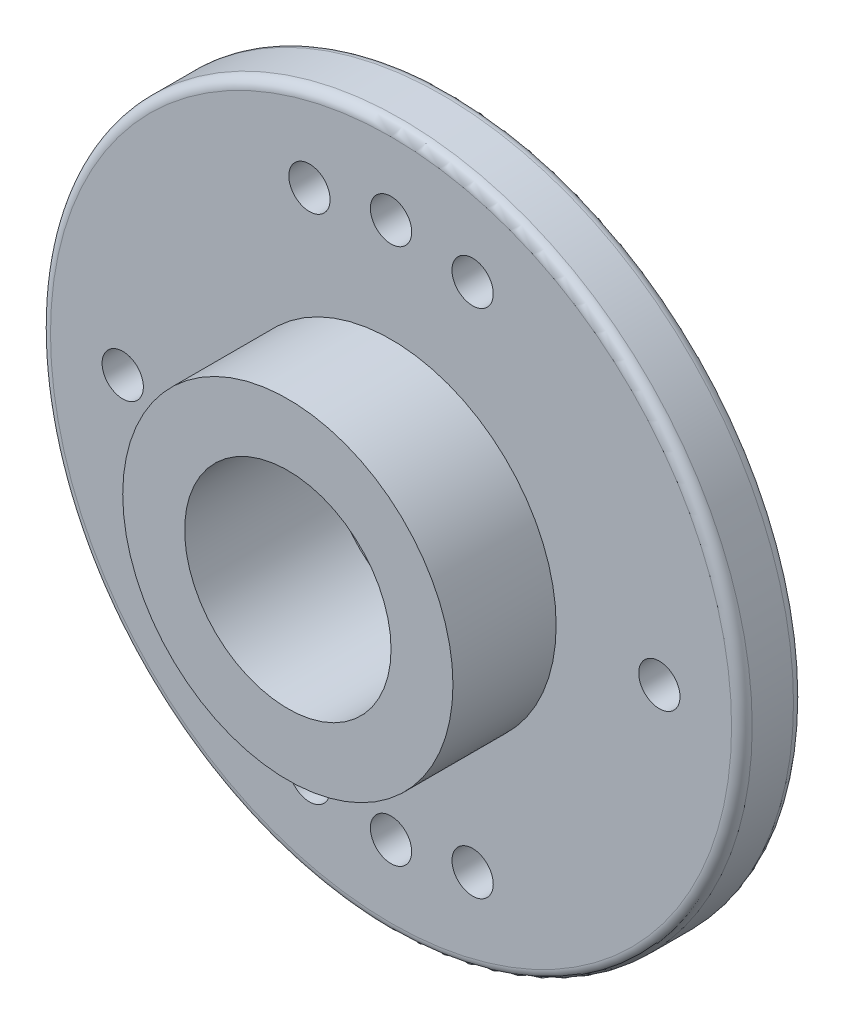
SolidWorks part; units mm, degrees
material "Nylon 101"
ref_plane "Front Plane" through (0, 0, 0) normal (0, 0, 1) x (1, 0, 0)
ref_plane "Top Plane" through (0, 0, 0) normal (0, 1, 0) x (1, 0, 0)
ref_plane "Right Plane" through (0, 0, 0) normal (1, 0, 0) x (0, 0, -1)
sketch "Sketch1" plane through (0, 0, 0) normal (0, 0, 1) x (1, 0, 0)
  line L0 (-8.5, 0) -> (8.5, 0) construction
  line L1 (0, 8.5) -> (0, -8.5) construction
  line L2 (-2.5842, 8.0976) -> (0, 0) construction
  line L3 (2.5842, 8.0976) -> (0, 0) construction
  line L4 (0, 0) -> (-2.5842, -8.0976) construction
  line L5 (0, 0) -> (2.5842, -8.0976) construction
  circle A0 centre (0, 0) radius 8.5
  circle A1 centre (0, 0) radius 1.25
  circle A2 centre (0, 0) radius 3
  circle A3 centre (0, 0) radius 3.5
  circle A4 centre (0, 6.5) radius 0.5
  circle A5 centre (0, -6.5) radius 0.5
  circle A6 centre (-6.5, 0) radius 0.5
  circle A7 centre (6.5, 0) radius 0.5
  circle A8 centre (-1.9762, 6.1923) radius 0.5
  circle A9 centre (1.9762, 6.1923) radius 0.5
  circle A10 centre (-1.9762, -6.1923) radius 0.5
  circle A11 centre (1.9762, -6.1923) radius 0.5
  circle A12 centre (0, 0) radius 4
  circle A13 centre (0, 0) radius 2.5
  dimension "D1" = 17
  dimension "D2" = 2.5
  dimension "D3" = 6
  dimension "D4" = 7
  dimension "D5" = 1
  dimension "D16" = 8
  dimension "D17" = 5
  dimension "D6" = 2
  dimension "D7" = 2
  dimension "D8" = 2
  dimension "D9" = 2
  dimension "D10" = 2
  dimension "D11" = 2
  dimension "D12" = 2
  dimension "D13" = 2
  dimension "D14" = 2
  dimension "D15" = 2
extrude "Boss-Extrude1" add sketch "Sketch1" along normal blind 0.5 contours A0 A12 A11 A10 A9 A8 A7 A6 A5 A4 | A12 A3 | A3 A2 | A2 A13 | A13 A1 region at (-8.2596, 0, 0) region at (-2.9151, 0, 0) region at (-3.401, 0, 0) region at (-3.8869, 0, 0) region at (-2.4293, 0, 0)
extrude "Boss-Extrude2" add sketch "Sketch1<4>" along normal blind 1.5 contours A0 A12 A11 A10 A9 A8 A7 A6 A5 A4 | A12 A3 | A3 A2 | A2 A13 region at (-8.2596, 0, 0) region at (-2.9151, 0, 0) region at (-3.401, 0, 0) region at (-3.8869, 0, 0)
sketch "Sketch1<4>" plane through (0, 0, 0) normal (0, 0, 1) x (1, 0, 0) same geometry as "Sketch1"
extrude "Boss-Extrude3" add sketch "Sketch1<5>" along normal blind 4 contours A12 A3 | A3 A2 | A2 A13 region at (-2.9151, 0, 0) region at (-3.401, 0, 0) region at (-3.8869, 0, 0)
sketch "Sketch1<5>" plane through (0, 0, 0) normal (0, 0, 1) x (1, 0, 0) same geometry as "Sketch1"
extrude "Boss-Extrude4" add sketch "Sketch1<6>" against normal blind 1 contours A3 A2 region at (-3.401, 0, 0)
sketch "Sketch1<6>" plane through (0, 0, 0) normal (0, 0, 1) x (1, 0, 0) same geometry as "Sketch1"
fillet "Fillet1" radius 0.25 4 edges at (8.5, 0, 1.5) (8.5, 0, 0) (3, 0, -1) (3.5, 0, -1)
